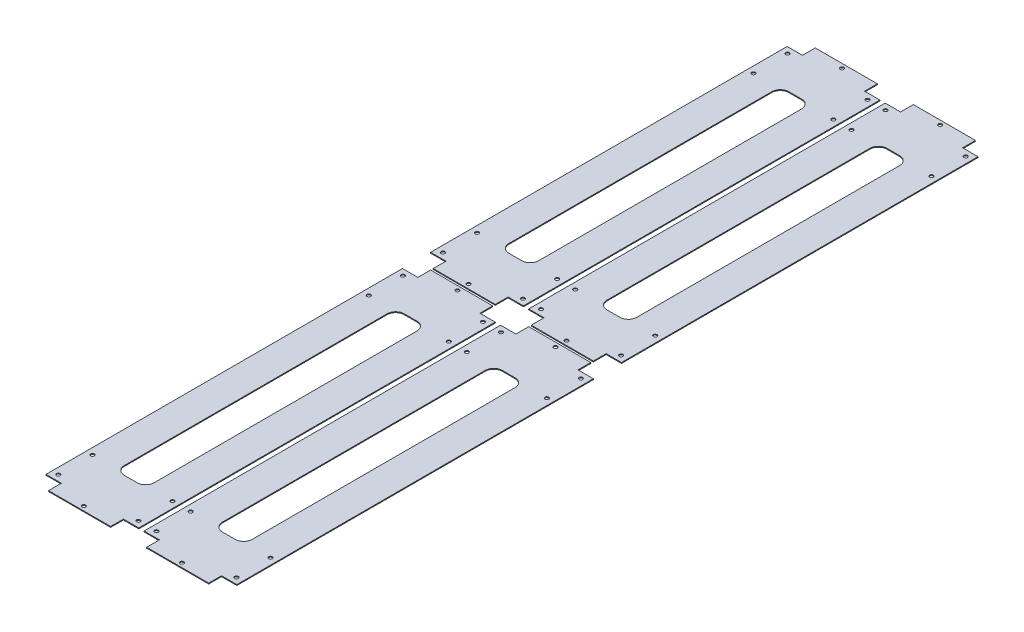
SolidWorks part; units mm, degrees
ref_plane "Front Plane" through (0, 0, 0) normal (0, 0, 1) x (1, 0, 0)
ref_plane "Top Plane" through (0, 0, 0) normal (0, 1, 0) x (1, 0, 0)
ref_plane "Right Plane" through (0, 0, 0) normal (1, 0, 0) x (0, 0, -1)
sketch "Sketch1" plane through (0, 0, 0) normal (0, 1, 0) x (1, 0, 0)
  line L0 (0, 223.995) -> (0, -223.995) construction
  line L1 (-54.4, -208.995) -> (-36.4, -208.995)
  line L3 (-36.4, 208.995) -> (-54.4, 208.995)
  line L4 (-54.4, 208.995) -> (-54.4, -208.995)
  line L12 (-36.4, -223.995) -> (36.4, -223.995)
  line L16 (36.4, -208.995) -> (54.4, -208.995)
  line L17 (54.4, -208.995) -> (54.4, 208.995)
  line L22 (36.4, 223.995) -> (-36.4, 223.995)
  line L25 (54.4, 208.995) -> (36.4, 208.995)
  line L26 (36.4, 208.995) -> (36.4, -208.995) construction
  line L27 (-17.5, 0) -> (0, 0) construction
  line L29 (-36.4, -223.995) -> (-36.4, -208.995)
  line L30 (36.4, -223.995) -> (36.4, -208.995)
  line L31 (-36.4, -208.995) -> (36.4, -208.995) construction
  line L34 (-36.4, 223.995) -> (-36.4, 208.995)
  line L35 (-36.4, 208.995) -> (36.4, 208.995) construction
  line L36 (36.4, 208.995) -> (36.4, 223.995)
  line L37 (-36.4, -208.995) -> (-36.4, 208.995) construction
  line L38 (0, 0) -> (17.5, 0) construction
  line L41 (-17.5, 0) -> (-54.4, 0) construction
  line L42 (-17.5, 164.0881) -> (17.5, 164.0881)
  line L43 (-17.5, 164.0881) -> (-17.5, -164.0881)
  line L44 (-17.5, -164.0881) -> (17.5, -164.0881)
  line L45 (17.5, 164.0881) -> (17.5, -164.0881)
  line L46 (-17.5, 164.0881) -> (17.5, -164.0881) construction
  line L47 (-17.5, -164.0881) -> (17.5, 164.0881) construction
  line L48 (46.9, -161.995) -> (-46.9, -161.995) construction
  line L49 (46.9, -161.995) -> (46.9, 161.995) construction
  line L50 (46.9, 161.995) -> (-46.9, 161.995) construction
  line L51 (-46.9, -161.995) -> (-46.9, 161.995) construction
  line L52 (46.9, -161.995) -> (-46.9, 161.995) construction
  line L53 (46.9, 161.995) -> (-46.9, -161.995) construction
  line L54 (46.9, 201.995) -> (-46.9, 201.995) construction
  line L55 (46.9, 201.995) -> (46.9, -201.995) construction
  line L56 (46.9, -201.995) -> (-46.9, -201.995) construction
  line L57 (-46.9, 201.995) -> (-46.9, -201.995) construction
  line L58 (46.9, 201.995) -> (-46.9, -201.995) construction
  line L59 (46.9, -201.995) -> (-46.9, 201.995) construction
  line L60 (17.5, 0) -> (54.4, 0) construction
  circle A2 centre (-46.9, 161.995) radius 2.15
  circle A3 centre (46.9, 161.995) radius 2.15
  circle A4 centre (-46.9, -161.995) radius 2.15
  circle A5 centre (46.9, -161.995) radius 2.15
  circle A6 centre (-46.9, -201.995) radius 2.15
  circle A7 centre (46.9, -201.995) radius 2.15
  circle A8 centre (46.9, 201.995) radius 2.15
  circle A9 centre (-46.9, 201.995) radius 2.15
  circle A10 centre (0, 218.995) radius 2.15
  circle A11 centre (0, -218.995) radius 2.15
  point P0 (0, 0)
  point P37 (0, 0)
  point P40 (0, 0)
  dimension "D5" = 40
  dimension "D12" = 4.3
  dimension "D2" = 7
  dimension "D13" = 10
  dimension "D6" = 10
  dimension "D3" = 10.5
  dimension "D4" = 18
  dimension "D7" = 403.99
  dimension "D8" = 15
  dimension "D9" = 72.8
  dimension "D10" = 35
  dimension "D11" = 328.1761
  dimension "D14" = 10.5
  dimension "D15" = 93.8
  dimension "D16" = 18
  dimension "D17" = 15
extrude "Boss-Extrude1" add sketch "Sketch1" along normal blind 1
fillet "Fillet2" radius 10 4 edges at (17.5, 0.5, -164.0881) (-17.5, 0.5, -164.0881) (17.5, 0.5, 164.0881) (-17.5, 0.5, 164.0881)
pattern_linear "LPattern2" count 2 spacing 115 along (1, 0, 0) count 2 spacing 451 along (0, 0, -1) of bodies 101
